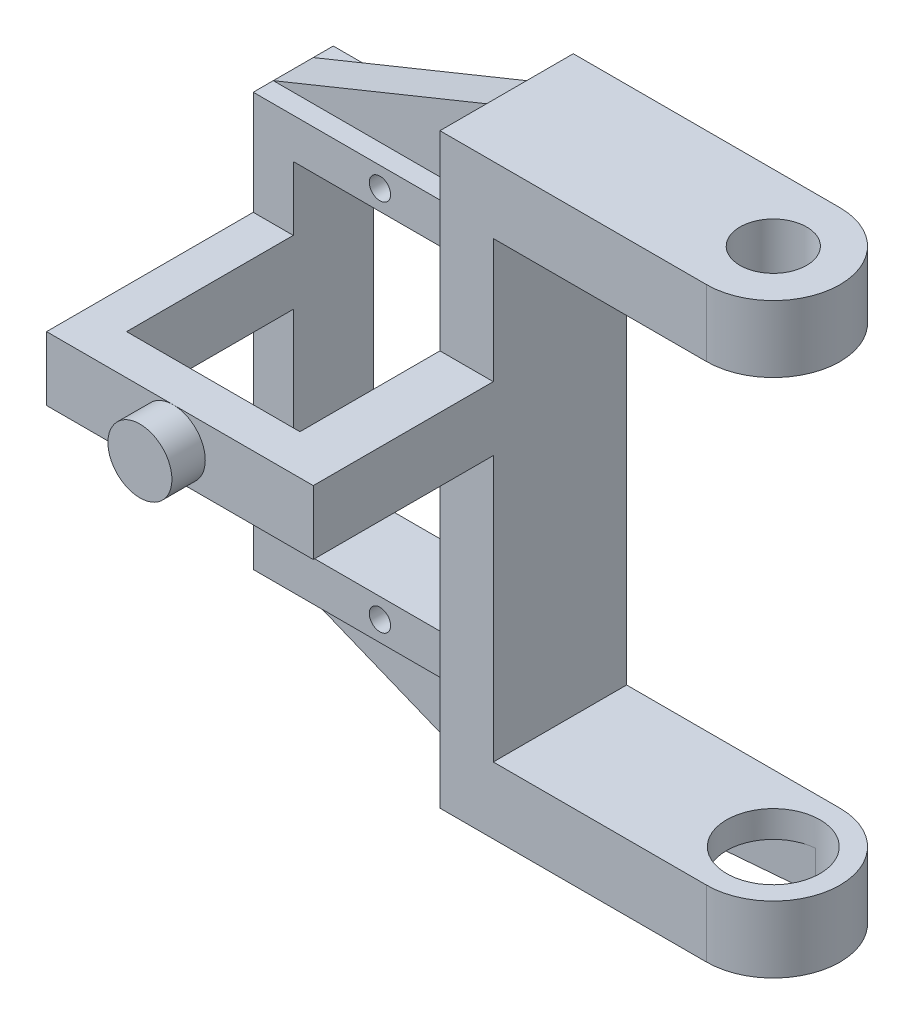
SolidWorks part; units mm, degrees
ref_plane "Front Plane" through (0, 0, 0) normal (0, 0, 1) x (1, 0, 0)
ref_plane "Top Plane" through (0, 0, 0) normal (0, 1, 0) x (1, 0, 0)
ref_plane "Right Plane" through (0, 0, 0) normal (1, 0, 0) x (0, 0, -1)
sketch "Sketch2" plane through (0, 0, 0) normal (0, 1, 0) x (1, 0, 0)
  line L1 (-12.5, 5) -> (12.5, 5)
  line L2 (-12.5, 5) -> (-12.5, -5)
  line L3 (-12.5, -5) -> (12.5, -5)
  line L4 (12.5, 5) -> (12.5, -5)
  line L5 (-12.5, 5) -> (12.5, -5) construction
  line L6 (-12.5, -5) -> (12.5, 5) construction
  point P0 (0, 0)
  dimension "D1" = 25
  dimension "D2" = 10
extrude "Boss-Extrude1" add sketch "Sketch2" along normal blind 5
fillet "Fillet1" 2 edges at (12.5, 2.5, 5) (12.5, 2.5, -5) type full round first side face at (0, 2.5, 5) second side face at (0, 2.5, -5) middle face at (12.5, 2.5, 0)
sketch "Sketch3" plane through (0, 5, 0) normal (0, 1, 0) x (1, 0, 0)
  line L0 (-12.5, -5) -> (7.5, -5) construction
  line L1 (-12.5, 5) -> (-8.5, 5)
  line L2 (-12.5, 5) -> (-12.5, -5)
  line L3 (-12.5, -5) -> (-8.5, -5)
  line L4 (-8.5, 5) -> (-8.5, -5)
  dimension "D1" = 4
extrude "Boss-Extrude2" add sketch "Sketch3" along normal blind 17
mirror "Mirror1" about plane through (0, 22, 0) normal (0, 1, 0) of bodies 102
sketch "Sketch12" plane through (0, 44, 0) normal (0, 1, 0) x (1, 0, 0)
  circle A1 centre (7.5, 0) radius 2.5
extrude "Cut-Extrude3" cut sketch "Sketch12" against normal blind 5
sketch "Sketch13" plane through (0, 0, 0) normal (0, -1, 0) x (1, 0, 0)
  line L0 (-8.7826, 2.092) -> (7.1957, 3.4867)
  line L1 (7.5, 0) -> (-8.6, 0)
  line L2 (-8.7826, -2.092) -> (7.1957, -3.4867)
  circle A1 centre (7.5, 0) radius 3.5
  circle A2 centre (-8.6, 0) radius 2.1
  dimension "D1" = 16.1
extrude "Cut-Extrude4" cut sketch "Sketch13" against normal blind 3 contours A2 | A2 L1 A1 L0 | A2 L2 A1 L1 | A1 region at (-0.7994, 0, 1.4778) region at (-7.2212, 0, 1.5044) region at (9.7979, 0, 2.5073) region at (-0.7994, 0, -1.4778)
sketch "Sketch14" plane through (0, 3, 0) normal (0, -1, 0) x (1, 0, 0)
  circle A0 centre (7.5, 0) radius 3.5
extrude "Cut-Extrude5" cut sketch "Sketch14" against normal blind 2
sketch "Sketch15" plane through (-12.5, 0, 0) normal (-1, 0, 0) x (0, 0, 1)
  line L0 (-5, 22) -> (5, 22)
  line L1 (-5, 44) -> (-5, 0) construction
  line L2 (5, 44) -> (5, 0) construction
  line L3 (5, 37.5) -> (-5, 37.5)
  line L4 (5, 22) -> (-5, 22)
  line L5 (5, 37.5) -> (5, 6.5)
  line L6 (5, 6.5) -> (-5, 6.5)
  line L7 (-5, 37.5) -> (-5, 6.5)
  line M7 (5, 0) -> (5, 44)
  line M9 (-5, 44) -> (-5, 0)
  dimension "D1" = 15.5
extrude "Boss-Extrude3" add sketch "Sketch15" along normal blind 16 contours L6 L0 M7 M9 | L3 L0 M7 M9 region at (-12.5, 29.75, 0) region at (-12.5, 14.25, 0)
sketch "Sketch16" plane through (0, 6.5, 0) normal (0, -1, 0) x (1, 0, 0)
  line L0 (-12.5, 5) -> (-12.5, -5) construction
  line L1 (-28.5, -5) -> (-12.5, -5)
  line L2 (-28.5, -5) -> (-28.5, -3)
  line L3 (-28.5, -3) -> (-12.5, -3)
  line L4 (-12.5, -5) -> (-12.5, -3)
  line L5 (-28.5, 0) -> (-12.5, 0)
  line L6 (-28.5, 5) -> (-28.5, -5) construction
  line L7 (-28.5, 3) -> (-12.5, 3)
  line L8 (-12.5, 5) -> (-12.5, 3)
  line L9 (-28.5, 5) -> (-12.5, 5)
  line L10 (-28.5, 5) -> (-28.5, 3)
  line M6 (-12.5, -5) -> (-12.5, 5)
  line M7 (-12.5, 5) -> (-28.5, 5)
  line M8 (-28.5, 5) -> (-28.5, -5)
  line M9 (-28.5, -5) -> (-12.5, -5)
  dimension "D1" = 2
extrude "Cut-Extrude6" cut sketch "Sketch16" against normal blind 31 contours L7 M8 M6 M7 | L3 M8 M9 M6 region at (-20.5, 6.5, -4) region at (-20.5, 6.5, 4)
sketch "Sketch18" plane through (0, 0, -3) normal (0, 0, -1) x (-1, 0, 0)
  line L23 (12.5, 9.5) -> (25.5, 9.5)
  line L24 (25.5, 9.5) -> (25.5, 34.5)
  line L25 (25.5, 34.5) -> (12.5, 34.5)
  line L26 (12.5, 9.5) -> (25.5, 9.5)
  line L27 (25.5, 9.5) -> (25.5, 34.5)
  line L28 (25.5, 34.5) -> (12.5, 34.5)
  line M11 (12.5, 37.5) -> (12.5, 6.5)
  dimension "D1" = 3
extrude "Cut-Extrude9" cut sketch "Sketch18" against normal blind 6 and the other way through all contours L27 L28 L26 M11 region at (-19, 22, -3)
sketch "Sketch20" plane through (0, 0, 0) normal (0, 0, 1) x (1, 0, 0)
  line L0 (-28.5, 37.5) -> (-12.5, 44)
rib "Rib1" sketch "Sketch20" sketch "Sketch20" thickness 3 extrusion direction parallel to sketch draft on no parameters "D1"=3
sketch "Sketch21" plane through (0, 0, 0) normal (0, 0, 1) x (1, 0, 0)
  line L0 (-28.5, 6.5) -> (-12.5, 0)
rib "Rib2" sketch "Sketch21" sketch "Sketch21" thickness 3 extrusion direction parallel to sketch draft on no parameters "D1"=3
sketch "Sketch22" plane through (0, 0, 3) normal (0, 0, 1) x (1, 0, 0)
  circle A0 centre (-19, 36) radius 0.8
  circle A1 centre (-19, 8) radius 0.8
extrude "Cut-Extrude10" cut sketch "Sketch22" against normal blind 6 contours A0 | A1
sketch "Sketch38" plane through (0, 0, 3) normal (0, 0, 1) x (1, 0, 0)
  line L1 (-25.5, 9.5) -> (-25.5, 34.5) construction
  line L2 (-25.5, 27.3) -> (-25.5, 24.9)
  line L3 (-25.5, 27.3) -> (-25.5, 29.7)
  line L4 (-25.5, 29.7) -> (-28.5, 29.7)
  line L5 (-28.5, 37.5) -> (-28.5, 6.5) construction
  line L6 (-25.5, 24.9) -> (-28.5, 24.9)
  line L7 (-28.5, 29.7) -> (-28.5, 24.9)
extrude "Boss-Extrude4" add sketch "Sketch38" along normal blind 15.5
sketch "Sketch39" plane through (-25.5, 0, 0) normal (1, 0, 0) x (0, 0, -1)
  line L0 (-18.5, 24.9) -> (-3, 24.9) construction
  line L5 (-18.5, 29.7) -> (-15.5, 29.7)
  line L6 (-18.5, 29.7) -> (-18.5, 24.9)
  line L7 (-18.5, 24.9) -> (-15.5, 24.9)
  line L8 (-15.5, 29.7) -> (-15.5, 24.9)
  dimension "D1" = 3
extrude "Boss-Extrude5" add sketch "Sketch39" along normal blind 17
sketch "Sketch42" plane through (0, 0, 15.5) normal (0, 0, -1) x (-1, 0, 0)
  line L0 (8.5, 24.9) -> (25.5, 24.9) construction
  line L1 (8.5, 29.7) -> (12.5, 29.7)
  line L2 (8.5, 29.7) -> (8.5, 24.9)
  line L3 (8.5, 24.9) -> (12.5, 24.9)
  line L4 (12.5, 29.7) -> (12.5, 24.9)
  dimension "D1" = 4
extrude "Boss-Extrude6" add sketch "Sketch42" along normal blind 10.5
sketch "Sketch43" plane through (0, 0, 18.5) normal (0, 0, 1) x (1, 0, 0)
  circle A0 centre (-19, 27.3) radius 2.4
extrude "Boss-Extrude7" add sketch "Sketch43" along normal blind 2.5
